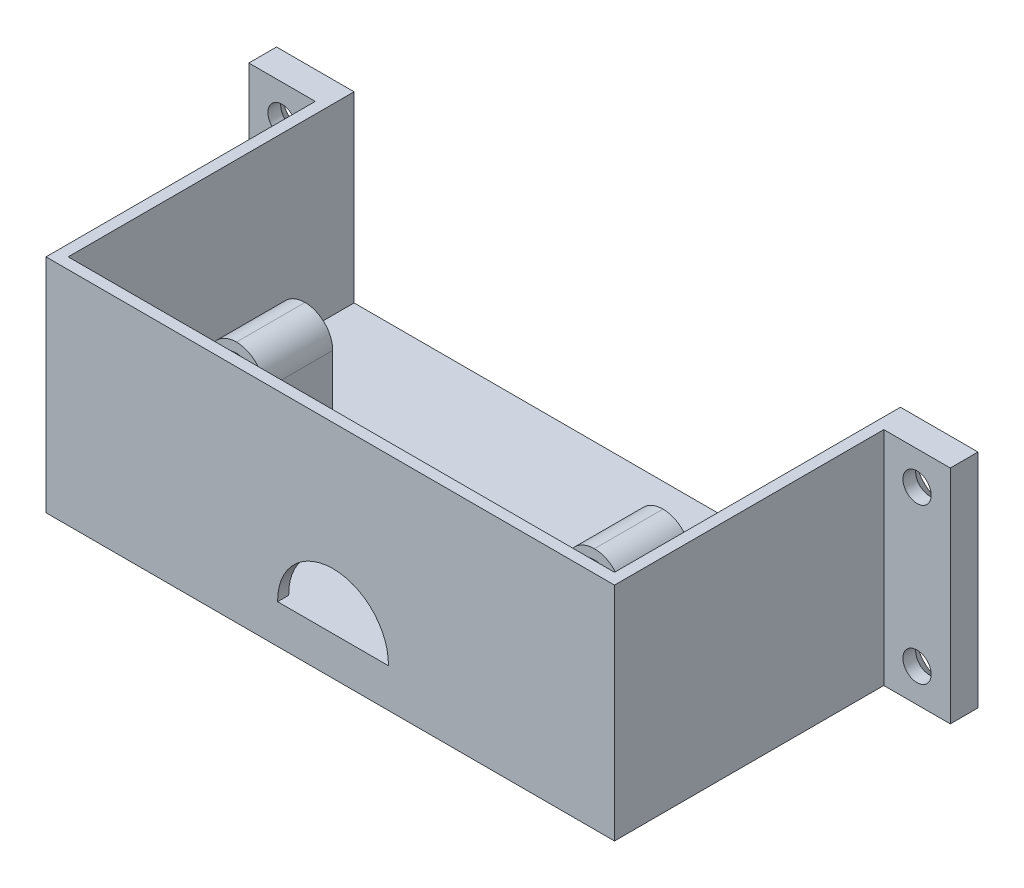
SolidWorks part; units mm, degrees
ref_plane "Plan de face" through (0, 0, 0) normal (0, 0, 1) x (1, 0, 0)
ref_plane "Plan de dessus" through (0, 0, 0) normal (0, 1, 0) x (1, 0, 0)
ref_plane "Plan de droite" through (0, 0, 0) normal (1, 0, 0) x (0, 0, -1)
sketch "Esquisse1" plane through (0, 0, 0) normal (0, 0, 1) x (1, 0, 0)
  line L1 (-17.4678, 19.1867) -> (85.1322, 19.1867)
  line L2 (-17.4678, 19.1867) -> (-17.4678, -15.8133)
  line L3 (-17.4678, -15.8133) -> (85.1322, -15.8133)
  line L4 (85.1322, 19.1867) -> (85.1322, -15.8133)
  dimension "D1" = 35
  dimension "D2" = 102.6
extrude "Boss.-Extru.1" add sketch "Esquisse1" along normal blind 53.6 and the other way blind 0.0001
sketch "Esquisse4" plane through (0, 19.1867, 0) normal (0, 1, 0) x (1, 0, 0)
  line L1 (-15.4678, -51.5999) -> (83.1322, -51.5999)
  line L2 (-15.4678, -51.5999) -> (-15.4678, 0.0001)
  line L3 (-15.4678, 0.0001) -> (83.1322, 0.0001)
  line L4 (83.1322, -51.5999) -> (83.1322, 0.0001)
  line L5 (-17.4678, -53.6) -> (-17.4678, 0.0001) construction
  line L6 (85.1322, -53.6) -> (85.1322, 0.0001) construction
  line L7 (85.1322, 0.0001) -> (-17.4678, 0.0001) construction
  dimension "D1" = 51.6
  dimension "D2" = 98.6
  dimension "D3" = 0
  dimension "D4" = 2
  dimension "D5" = 2
extrude "Enlèv. mat.-Extru.2" cut sketch "Esquisse4" against normal blind 33
sketch "Esquisse9" plane through (0, -13.8133, 0) normal (0, 1, 0) x (1, 0, 0)
  line L0 (83.1322, 0.0001) -> (-15.4678, 0.0001) construction
  line L1 (-3.4678, -25.8499) -> (6.5322, -25.8499)
  line L2 (-3.4678, -25.8499) -> (-3.4678, -38.2299)
  line L3 (-3.4678, -38.2299) -> (6.5322, -38.2299)
  line L4 (6.5322, -25.8499) -> (6.5322, -38.2299)
  line L5 (-15.4678, 0.0001) -> (-15.4678, -51.5999) construction
  line L11 (61.1322, -25.8499) -> (71.1322, -25.8499)
  line L12 (61.1322, -25.8499) -> (61.1322, -38.2299)
  line L13 (61.1322, -38.2299) -> (71.1322, -38.2299)
  line L14 (71.1322, -25.8499) -> (71.1322, -38.2299)
  line L19 (83.1322, -51.5999) -> (83.1322, 0.0001) construction
  dimension "D1" = 25.85
  dimension "D2" = 10
  dimension "D3" = 12
  dimension "D4" = 12.38
  dimension "D10" = 25.85
  dimension "D11" = 12.38
  dimension "D13" = 10
  dimension "D16" = 12
extrude "Boss.-Extru.3" add sketch "Esquisse9" along normal blind 21.5
fillet "Congé1" radius 5 4 edges at (-3.4678, 7.6867, 32.0399) (6.5322, 7.6867, 32.0399) (71.1322, 7.6867, 32.0399) (61.1322, 7.6867, 32.0399)
sketch "Esquisse10" plane through (0, 0, 25.8499) normal (0, 0, -1) x (-1, 0, 0)
  line L0 (-71.1322, -13.8133) -> (-61.1322, -13.8133) construction
  line L2 (-83.1322, -13.8133) -> (15.4678, -13.8133) construction
  line L4 (-71.1322, 2.6867) -> (-71.1322, -13.8133) construction
  line L6 (3.4678, 2.6867) -> (3.4678, -13.8133) construction
  line L7 (-83.1322, -13.8133) -> (-83.1322, 19.1867) construction
  line L8 (15.4678, -13.8133) -> (15.4678, 19.1867) construction
  circle A0 centre (-66.1322, 2.1867) radius 3.75
  circle A1 centre (-1.5322, 2.1867) radius 3.75
  point P4 (-66.1322, -13.8133)
  dimension "D1" = 7.5
  dimension "D4" = 7.5
  dimension "D2" = 16
  dimension "D3" = 5
  dimension "D5" = 16
  dimension "D6" = 5
  dimension "D7" = 64.6
  dimension "D8" = 17
  dimension "D9" = 17
extrude "Enlèv. mat.-Extru.4" cut sketch "Esquisse10" against normal blind 15
sketch "Esquisse18" plane through (0, 0, 53.6) normal (0, 0, 1) x (1, 0, 0)
  line L0 (85.1322, -15.8133) -> (85.1322, 19.1867) construction
  line L1 (-17.4678, -15.8133) -> (85.1322, -15.8133) construction
  line L2 (24.3335, -13.8133) -> (44.3308, -13.8133)
  arc A1 (44.3308, -13.8133) -> (24.3335, -13.8133) centre (34.3322, -13.6433) ccw
  dimension "D3" = 50.8
  dimension "D4" = 2
extrude "Enlèv. mat.-Extru.5" cut sketch "Esquisse18" against normal blind 2.1
sketch "Esquisse19" plane through (0, -15.8133, 0) normal (0, -1, 0) x (1, 0, 0)
  line L1 (85.1322, -0.0001) -> (-17.4678, -0.0001)
  line L2 (85.1322, -0.0001) -> (85.1322, 53.6)
  line L3 (85.1322, 53.6) -> (-17.4678, 53.6)
  line L4 (-17.4678, -0.0001) -> (-17.4678, 53.6)
extrude "Boss.-Extru.4" add sketch "Esquisse19" along normal blind 5
sketch "Esquisse21" plane through (-17.4678, 0, 0) normal (-1, 0, 0) x (0, 0, 1)
  line L0 (53.6, -20.8133) -> (-0.0001, -20.8133) construction
  line L1 (-0.0001, 19.1867) -> (4.9999, 19.1867)
  line L2 (-0.0001, 19.1867) -> (-0.0001, -20.8133)
  line L3 (-0.0001, -20.8133) -> (4.9999, -20.8133)
  line L4 (4.9999, 19.1867) -> (4.9999, -20.8133)
  dimension "D1" = 5
extrude "Boss.-Extru.5" add sketch "Esquisse21" along normal blind 12
sketch "Esquisse22" plane through (85.1322, 0, 0) normal (1, 0, 0) x (0, 0, -1)
  line L0 (0.0001, -20.8133) -> (-53.6, -20.8133) construction
  line L1 (0.0001, 19.1867) -> (-4.9999, 19.1867)
  line L2 (0.0001, 19.1867) -> (0.0001, -20.8133)
  line L3 (0.0001, -20.8133) -> (-4.9999, -20.8133)
  line L4 (-4.9999, 19.1867) -> (-4.9999, -20.8133)
  dimension "D1" = 5
extrude "Boss.-Extru.6" add sketch "Esquisse22" along normal blind 12
sketch "Esquisse23" plane through (0, 0, -0.0001) normal (0, 0, -1) x (-1, 0, 0)
  line L0 (-97.1322, -20.8133) -> (-97.1322, 19.1867) construction
  line L2 (-97.1322, 19.1867) -> (-83.1322, 19.1867) construction
  line L3 (29.4678, -20.8133) -> (-97.1322, -20.8133) construction
  line L4 (29.4678, 19.1867) -> (29.4678, -20.8133) construction
  line L5 (15.4678, 19.1867) -> (29.4678, 19.1867) construction
  circle A0 centre (-91.1322, 13.1867) radius 5.25
  circle A1 centre (-91.1322, -14.8133) radius 5.25
  circle A2 centre (23.4678, 13.1867) radius 5.25
  circle A3 centre (23.4678, -14.8133) radius 5.25
  dimension "D3" = 10.5
  dimension "D10" = 10.5
  dimension "D11" = 10.5
  dimension "D12" = 10.5
  dimension "D1" = 6
  dimension "D2" = 6
  dimension "D4" = 6
  dimension "D5" = 6
  dimension "D6" = 6
  dimension "D7" = 6
  dimension "D8" = 6
  dimension "D9" = 6
hole_wizard "Fraisage pour vis à tête fraisée bombée #51" positions "Esquisse3D1" profile "Esquisse24" countersink size "#5" standard "Ansi Inch" end condition through all
sketch3d "Esquisse3D1"
  point P0 (91.1322, 13.1867, -0.0001)
  point P3 (91.1322, -14.8133, -0.0001)
  point P6 (-23.4678, 13.1867, -0.0001)
  point P9 (-23.4678, -14.8133, -0.0001)
sketch "Esquisse24" plane through (91.1322, 13.1867, -0.0001) normal (1, 0, 0) x (0, 1, 0)
  line L0 (0, 0) -> (0, 53.6001)
  line L1 (0, 53.6001) -> (2.55, 53.6001)
  line L2 (2.55, 53.6001) -> (2.55, 2.7)
  line L3 (2.55, 2.7) -> (5.25, 0)
  line L5 (5.25, 0) -> (0, 0)
  line L6 (-2.55, 2.7) -> (-5.25, 0) construction
  line L11 (0, -6.35) -> (0, 107.95) construction
  dimension "Diamètre du perçage jusqu'au prochain" = 5.1
  dimension "Profondeur du perçage jusqu'au prochain" = 53.6001
  dimension "Diamètre du fraisage entrant" = 10.5
  dimension "Angle du fraisage entrant" = 90
